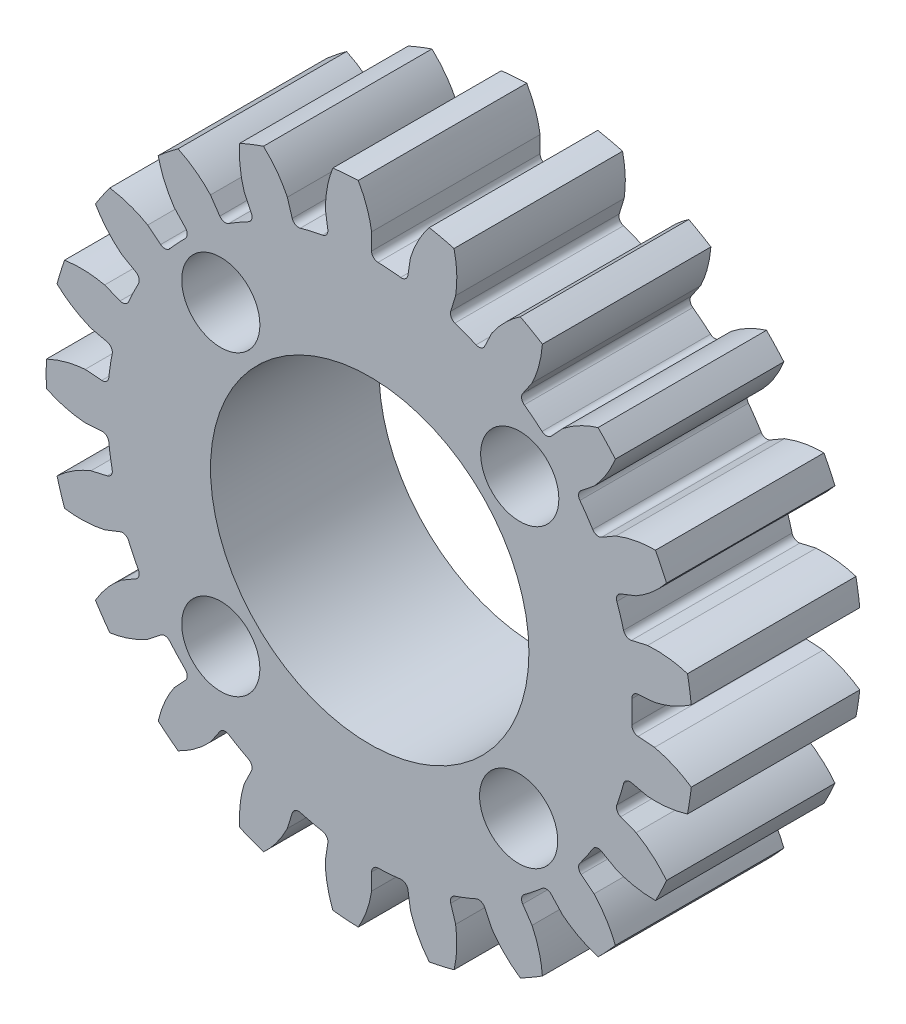
SolidWorks part; units mm, degrees
ref_plane "Front" through (0, 0, 0) normal (0, 0, 1) x (1, 0, 0)
ref_plane "Top" through (0, 0, 0) normal (0, 1, 0) x (1, 0, 0)
ref_plane "Right" through (0, 0, 0) normal (1, 0, 0) x (0, 0, -1)
sketch "Sketch1" plane through (0, 0, 0) normal (0, 0, 1) x (1, 0, 0)
  line L0 (-266.7, 0) -> (266.7, 0) construction
  circle A0 centre (0, 0) radius 12.192
  circle A1 centre (0, 0) radius 11.1125 construction
  circle A3 centre (0, 0) radius 9.888 construction
  dimension "D1" = 1.2245
  dimension "D2" = 2.304
  dimension "D3" = 1.0795
extrude "Boss-Extrude1" add sketch "Sketch1" against normal blind 6.35
sketch "Sketch2" plane through (0, 0, 0) normal (1, 0, 0) x (0, 0, -1)
  line L0 (6.35, 0) -> (14.2875, 0)
  line L1 (6.35, 0) -> (6.35, 9.525)
  line L2 (6.35, 9.525) -> (14.2875, 9.525)
  line L3 (14.2875, 9.525) -> (14.2875, 0)
  point P5 (14.2875, -9.525)
sketch "Sketch3" plane through (0, 0, 0) normal (0, 0, 1) x (1, 0, 0)
  line L0 (0, 0) -> (0, 12.192) construction
  line L1 (-2.6937, 10.4159) -> (0, 11.1125)
  line L2 (-9.5921, 11.1125) -> (9.5921, 11.1125) construction
  line L3 (-9.2865, 8.7108) -> (9.2865, 13.5142) construction
  line L4 (-2.6937, 10.4159) -> (0, 0) construction
  line L5 (-6.6544, 8.4537) -> (0, 0) construction
  line L6 (-6.6544, 8.4537) -> (-0.9701, 12.9282) construction
  line L7 (-1.8783, 10.5933) -> (0, 0) construction
  line L8 (-1.8783, 10.5933) -> (0.0394, 10.9333) construction
  arc A0 (-2.6937, 10.4159) -> (-6.6544, 8.4537) centre (0, 0) ccw
  circle A1 centre (0, 0) radius 11.1125 construction
  circle A2 centre (0, 0) radius 10.7585 construction
  arc A3 (-2.6937, 10.4159) -> (-1.8783, 10.5933) centre (0, 0) cw
  circle A4 centre (0, 0) radius 12.192 construction
  point P6 (0, 11.1125)
  dimension "D1" = 2.7823
  dimension "Pressure Angle" = 14.5
  dimension "D2" = 4.4518
  dimension "D3" = 7.2341
  dimension "D4" = 0.8347
  dimension "D5" = 1.9476
sketch "Sketch4" plane through (0, 0, 0) normal (0, 0, 1) x (1, 0, 0)
  line L0 (0, 0) -> (0.8281, 11.0504) construction
  line L1 (0.0699, 10.7583) -> (0.0699, 9.8878)
  line L2 (0, 11.1125) -> (1.6562, 10.9884) construction
  line L3 (1.5343, 10.6486) -> (1.4046, 9.7877)
  line L4 (0.0699, 9.8878) -> (0, 0) construction
  line L5 (0, 0) -> (0, 12.192) construction
  arc A0 (1.4046, 9.7877) -> (0.0699, 9.8878) centre (0, 0) ccw
  arc A1 (0, 11.1125) -> (1.6562, 10.9884) centre (0, 0) cw construction
  circle A2 centre (0, 0) radius 11.1125 construction
  circle A3 centre (0, 0) radius 10.7585 construction
  circle A4 centre (0, 0) radius 9.888 construction
  arc A5 (2.8861, 12.6392) -> (-0.9701, 12.9282) centre (0, 0) ccw
  spline S0 degree 2 poles (-0.9701, 12.9282) (-0.1124, 11.9553) (0.0699, 10.7583) knots 0 0 0 1 1 1
  spline S1 degree 2 poles (2.8861, 12.6392) (1.893, 11.8051) (1.5343, 10.6486) knots 0 0 0 1 1 1
  dimension "D1" = 1.6624
extrude "Cut-Extrude1" cut sketch "Sketch4" against normal through all
fillet "Fillet1" radius 0.2494 2 edges at (1.4046, 9.7877, -3.175) (0.0699, 9.8878, -3.175)
pattern_circular "CirPattern1" count 21 over 360 about axis through (0, 0, -6.35) along (0, 0, 1) of "Cut-Extrude1", "Fillet1"
sketch "Sketch5" plane through (0, 0, 0) normal (0, 0, 1) x (1, 0, 0)
  circle A0 centre (0, 0) radius 6
  circle A1 centre (0, 0) radius 4.7625 construction
  dimension "Bore Min" = 12
  dimension "Bore Max" = 9.525
extrude "Cut-Extrude2" cut sketch "Sketch5" against normal through all
sketch "Pitch Dia" plane through (0, 0, 0) normal (0, 0, 1) x (1, 0, 0)
  circle A0 centre (0, 0) radius 11.1125 construction
  circle A1 centre (0, 0) radius 11.1125
sketch "Sketch6" plane through (0, 0, 0) normal (0, 0, 1) x (1, 0, 0)
  circle A0 centre (0, 0) radius 7.9375
  dimension "D1" = 15.875
hole_wizard "#4 Clearance Hole1" positions "Sketch7" profile "Sketch8" hole size "#4" standard "ANSI Inch"
sketch "Sketch7" plane through (0, 0, 0) normal (0, 0, 1) x (1, 0, 0)
  line L1 (-5.6127, 5.6127) -> (5.6127, 5.6127)
  line L2 (-5.6127, 5.6127) -> (-5.6127, -5.6127)
  line L3 (-5.6127, -5.6127) -> (5.6127, -5.6127)
  line L4 (5.6127, 5.6127) -> (5.6127, -5.6127)
  circle A0 centre (0, 0) radius 7.9375 construction
  point P0 (-5.6127, 5.6127)
  point P4 (5.6542, 5.5708)
  point P6 (5.6127, -5.6127)
  point P8 (-5.6127, -5.6127)
sketch "Sketch8" plane through (-5.6127, 5.6127, 0) normal (1, 0, 0) x (0, -1, 0)
  line L0 (0, 0) -> (0, 52.4472)
  line L1 (0, 52.4472) -> (1.4732, 51.562)
  line L2 (1.4732, 51.562) -> (1.4732, 0)
  line L5 (1.4732, 0) -> (0, 0)
  line L10 (0, 52.4472) -> (-1.4732, 51.562) construction
  line L11 (0, -6.35) -> (0, 107.95) construction
  dimension "Hole Dia." = 2.9464
  dimension "Hole Depth" = 51.562
  dimension "Drill Angle" = 118
equation "\"D1@Boss-Extrude1\" = \"Face Wd@Sketch2\""
equation "\"D1@Sketch4\" = 1.5708/(\"Number of Teeth@Sketch1\"/\"Ptich Dia@Sketch1\")"
equation "\"D1\" = \"B Hub Dia@Sketch2\" * .025"
equation "\"D1@CirPattern1\" = \"Number of Teeth@Sketch1\""
equation "\"D1@Fillet1\" = \"D1@Sketch4\"*.15"
equation "\"D1\" = \"OD@Sketch1\" * .01"
equation "\"D1@Sketch1\" = 1.157/(\"Number of Teeth@Sketch1\"/\"Ptich Dia@Sketch1\")"
